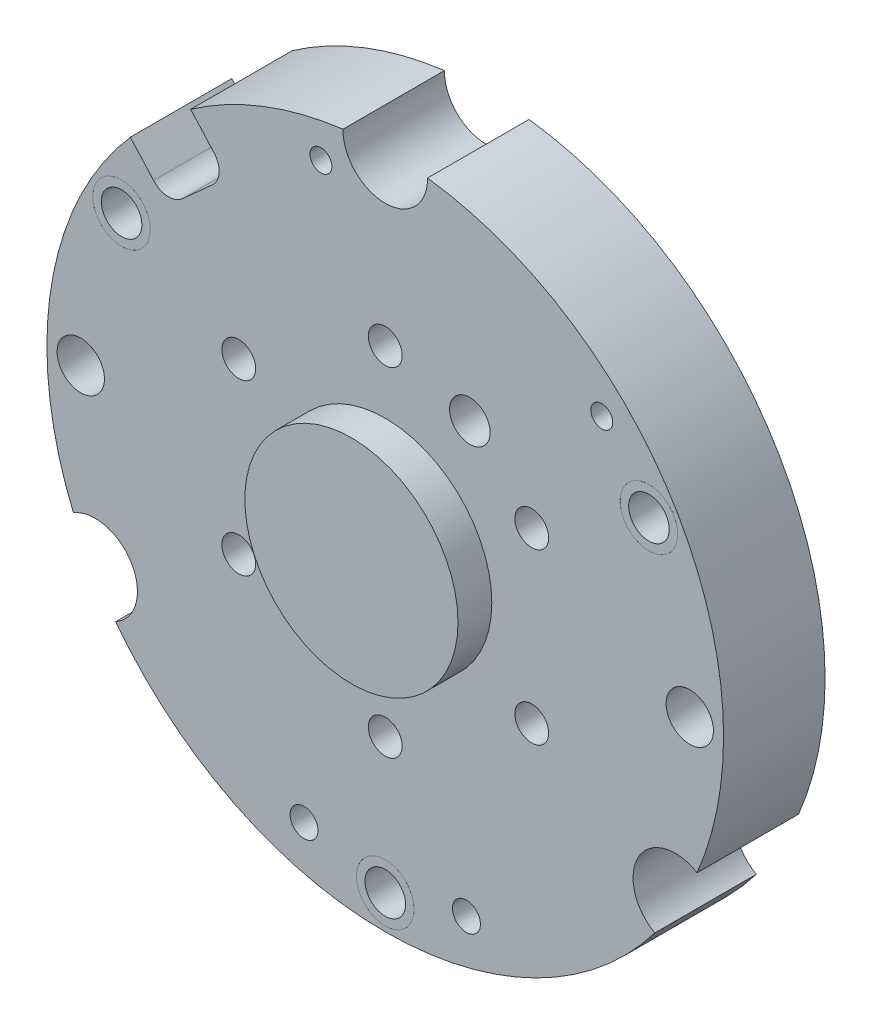
SolidWorks part; units mm, degrees
material "1060-H18"
ref_plane "Piano frontale" through (0, 0, 0) normal (0, 0, 1) x (1, 0, 0)
ref_plane "Piano superiore" through (0, 0, 0) normal (0, 1, 0) x (1, 0, 0)
ref_plane "Piano destro" through (0, 0, 0) normal (1, 0, 0) x (0, 0, -1)
sketch "Schizzo1" plane through (0, 0, 0) normal (0, 0, 1) x (1, 0, 0)
  line L3 (-34.2352, 29.0552) -> (-37.6736, 32.874)
  line L4 (-28.7559, 40.9035) -> (-25.3174, 37.0847)
  line L5 (-25.5395, 32.8479) -> (-29.9984, 28.8331)
  line L6 (-34.2352, 29.0552) -> (-37.6736, 32.874)
  line L7 (-28.7559, 40.9035) -> (-25.3174, 37.0847)
  line L8 (-25.5395, 32.8479) -> (-29.9984, 28.8331)
  arc A2 (32, 30.379) -> (32, 33.621) centre (32, 32) ccw
  arc A3 (32, 33.621) -> (32, 30.379) centre (32, 32) ccw
  arc A4 (32, 30.379) -> (32, 33.621) centre (32, 32) ccw
  arc A5 (32, 33.621) -> (32, 30.379) centre (32, 32) ccw
  arc A6 (-12, -44.067) -> (-12, -39.933) centre (-12, -42) ccw
  arc A7 (-12, -39.933) -> (-12, -44.067) centre (-12, -42) ccw
  arc A8 (-12, -44.067) -> (-12, -39.933) centre (-12, -42) ccw
  arc A9 (-34.2352, 29.0552) -> (-29.9984, 28.8331) centre (-32.0057, 31.0626) ccw
  arc A10 (-37.6736, 32.874) -> (-46.0866, -19.3913) centre (0, 0) ccw
  arc A11 (-39.8377, -30.2151) -> (-46.0866, -19.3913) centre (-42.87, -24.75) ccw
  arc A12 (-39.8377, -30.2151) -> (39.8377, -30.2151) centre (0, 0) ccw
  arc A13 (46.0866, -19.3913) -> (39.8377, -30.2151) centre (42.87, -24.75) ccw
  arc A14 (46.0866, -19.3913) -> (6.2491, 49.608) centre (0, 0) ccw
  arc A15 (-6.2491, 49.608) -> (6.2491, 49.608) centre (0, 49.5) ccw
  arc A16 (-6.2491, 49.608) -> (-28.7559, 40.9035) centre (0, 0) ccw
  arc A17 (-25.5395, 32.8479) -> (-25.3174, 37.0847) centre (-27.5469, 35.0773) ccw
  arc A18 (-34.2352, 29.0552) -> (-29.9984, 28.8331) centre (-32.0057, 31.0626) ccw
  arc A19 (-37.6736, 32.874) -> (-46.0866, -19.3913) centre (0, 0) ccw
  arc A20 (-39.8377, -30.2151) -> (-46.0866, -19.3913) centre (-42.87, -24.75) ccw
  arc A21 (-39.8377, -30.2151) -> (39.8377, -30.2151) centre (0, 0) ccw
  arc A22 (46.0866, -19.3913) -> (39.8377, -30.2151) centre (42.87, -24.75) ccw
  arc A23 (46.0866, -19.3913) -> (6.2491, 49.608) centre (0, 0) ccw
  arc A24 (-6.2491, 49.608) -> (6.2491, 49.608) centre (0, 49.5) ccw
  arc A25 (-6.2491, 49.608) -> (-28.7559, 40.9035) centre (0, 0) ccw
  arc A26 (-25.5395, 32.8479) -> (-25.3174, 37.0847) centre (-27.5469, 35.0773) ccw
  arc A27 (-12, -39.933) -> (-12, -44.067) centre (-12, -42) ccw
  arc A28 (12, -44.067) -> (12, -39.933) centre (12, -42) ccw
  arc A29 (12, -39.933) -> (12, -44.067) centre (12, -42) ccw
  arc A30 (12, -44.067) -> (12, -39.933) centre (12, -42) ccw
  arc A31 (12, -39.933) -> (12, -44.067) centre (12, -42) ccw
  arc A32 (-38.97, 26.75) -> (-38.97, 18.25) centre (-38.97, 22.5) ccw
  arc A33 (-38.97, 18.25) -> (-38.97, 26.75) centre (-38.97, 22.5) ccw
  arc A34 (-38.97, 26.75) -> (-38.97, 18.25) centre (-38.97, 22.5) ccw
  arc A35 (-38.97, 18.25) -> (-38.97, 26.75) centre (-38.97, 22.5) ccw
  arc A36 (38.97, 26.75) -> (38.97, 18.25) centre (38.97, 22.5) ccw
  arc A37 (38.97, 18.25) -> (38.97, 26.75) centre (38.97, 22.5) ccw
  arc A38 (38.97, 26.75) -> (38.97, 18.25) centre (38.97, 22.5) ccw
  arc A39 (38.97, 18.25) -> (38.97, 26.75) centre (38.97, 22.5) ccw
  arc A40 (0, -40.75) -> (0, -49.25) centre (0, -45) ccw
  arc A41 (0, -49.25) -> (0, -40.75) centre (0, -45) ccw
  arc A42 (0, -40.75) -> (0, -49.25) centre (0, -45) ccw
  arc A43 (0, -49.25) -> (0, -40.75) centre (0, -45) ccw
  arc A44 (-45, -3.5) -> (-45, 3.5) centre (-45, 0) ccw
  arc A45 (-45, 3.5) -> (-45, -3.5) centre (-45, 0) ccw
  arc A46 (-45, -3.5) -> (-45, 3.5) centre (-45, 0) ccw
  arc A47 (-45, 3.5) -> (-45, -3.5) centre (-45, 0) ccw
  arc A48 (45, -3.5) -> (45, 3.5) centre (45, 0) ccw
  arc A49 (45, 3.5) -> (45, -3.5) centre (45, 0) ccw
  arc A50 (45, -3.5) -> (45, 3.5) centre (45, 0) ccw
  arc A51 (45, 3.5) -> (45, -3.5) centre (45, 0) ccw
  arc A56 (-9.5, 42.379) -> (-9.5, 45.621) centre (-9.5, 44) ccw
  arc A57 (-9.5, 45.621) -> (-9.5, 42.379) centre (-9.5, 44) ccw
  arc A58 (-9.5, 42.379) -> (-9.5, 45.621) centre (-9.5, 44) ccw
  arc A59 (-9.5, 45.621) -> (-9.5, 42.379) centre (-9.5, 44) ccw
  dimension "D1" = 0
  dimension "D2" = 0
  dimension "D3" = 0
  dimension "D4" = 0
  dimension "D5" = 0
  dimension "D6" = 0
  dimension "D7" = 0
  dimension "D8" = 0
  dimension "D9" = 0
  dimension "D11" = 0
extrude "Estrusione-Estrusione1" add sketch "Schizzo1" along normal blind 15
sketch "Schizzo2" plane through (0, 0, 15) normal (0, 0, 1) x (1, 0, 0)
  arc A2 (-2.1651, -23.75) -> (2.1651, -26.25) centre (0, -25) ccw
  arc A3 (2.1651, -26.25) -> (-2.1651, -23.75) centre (0, -25) ccw
  arc A4 (-2.1651, -23.75) -> (2.1651, -26.25) centre (0, -25) ccw
  arc A5 (2.1651, -26.25) -> (-2.1651, -23.75) centre (0, -25) ccw
  arc A6 (19.4856, -11.25) -> (23.8157, -13.75) centre (21.6506, -12.5) ccw
  arc A7 (23.8157, -13.75) -> (19.4856, -11.25) centre (21.6506, -12.5) ccw
  arc A8 (19.4856, -11.25) -> (23.8157, -13.75) centre (21.6506, -12.5) ccw
  arc A9 (23.8157, -13.75) -> (19.4856, -11.25) centre (21.6506, -12.5) ccw
  arc A10 (19.4856, 13.75) -> (23.8157, 11.25) centre (21.6506, 12.5) ccw
  arc A11 (23.8157, 11.25) -> (19.4856, 13.75) centre (21.6506, 12.5) ccw
  arc A12 (19.4856, 13.75) -> (23.8157, 11.25) centre (21.6506, 12.5) ccw
  arc A13 (23.8157, 11.25) -> (19.4856, 13.75) centre (21.6506, 12.5) ccw
  arc A14 (9.9019, 23.1506) -> (15.0981, 20.1506) centre (12.5, 21.6506) ccw
  arc A15 (15.0981, 20.1506) -> (9.9019, 23.1506) centre (12.5, 21.6506) ccw
  arc A16 (9.9019, 23.1506) -> (15.0981, 20.1506) centre (12.5, 21.6506) ccw
  arc A17 (15.0981, 20.1506) -> (9.9019, 23.1506) centre (12.5, 21.6506) ccw
  arc A22 (-23.8157, -11.25) -> (-19.4856, -13.75) centre (-21.6506, -12.5) ccw
  arc A23 (-19.4856, -13.75) -> (-23.8157, -11.25) centre (-21.6506, -12.5) ccw
  arc A24 (-23.8157, -11.25) -> (-19.4856, -13.75) centre (-21.6506, -12.5) ccw
  arc A25 (-19.4856, -13.75) -> (-23.8157, -11.25) centre (-21.6506, -12.5) ccw
  arc A26 (-2.1651, 26.25) -> (2.1651, 23.75) centre (0, 25) ccw
  arc A27 (2.1651, 23.75) -> (-2.1651, 26.25) centre (0, 25) ccw
  arc A28 (-2.1651, 26.25) -> (2.1651, 23.75) centre (0, 25) ccw
  arc A29 (2.1651, 23.75) -> (-2.1651, 26.25) centre (0, 25) ccw
  arc A30 (-23.8157, 13.75) -> (-19.4856, 11.25) centre (-21.6506, 12.5) ccw
  arc A31 (-19.4856, 11.25) -> (-23.8157, 13.75) centre (-21.6506, 12.5) ccw
  arc A32 (-23.8157, 13.75) -> (-19.4856, 11.25) centre (-21.6506, 12.5) ccw
  arc A33 (-19.4856, 11.25) -> (-23.8157, 13.75) centre (-21.6506, 12.5) ccw
  dimension "D1" = 0
  dimension "D2" = 0
  dimension "D3" = 0
  dimension "D4" = 0
  dimension "D6" = 0
  dimension "D7" = 0
  dimension "D8" = 0
extrude "Taglio-Estrusione1" cut sketch "Schizzo2" against normal blind 15
sketch "Schizzo3" plane through (0, 0, 0) normal (0, 0, -1) x (-1, 0, 0)
  circle A74 centre (0, 25) radius 5.5
  circle A75 centre (0, 25) radius 5.5
  circle A85 centre (21.6506, 12.5) radius 5.5
  circle A86 centre (21.6506, -12.5) radius 5.5
  circle A87 centre (0, -25) radius 5.5
  circle A88 centre (-21.6506, -12.5) radius 5.5
  circle A89 centre (-21.6506, 12.5) radius 5.5
  dimension "D1" = 3
extrude "Taglio-Estrusione2" cut sketch "Schizzo3" against normal blind 5
sketch "Schizzo5" plane through (0, 0, 15) normal (0, 0, 1) x (1, 0, 0)
  arc A2 (13.6399, -7.875) -> (-13.6399, 7.875) centre (0, 0) ccw
  arc A3 (-13.6399, 7.875) -> (13.6399, -7.875) centre (0, 0) ccw
  arc A6 (13.6399, -7.875) -> (-13.6399, 7.875) centre (0, 0) ccw
  arc A7 (-13.6399, 7.875) -> (13.6399, -7.875) centre (0, 0) ccw
  dimension "D1" = 0
extrude "Estrusione-Estrusione2" add sketch "Schizzo5" along normal blind 5 separate body contours A7 A6
sketch "Schizzo6" plane through (0, 0, 0) normal (0, 0, -1) x (-1, 0, 0)
  circle A0 centre (0, 0) radius 35
extrude "Taglio-Estrusione3" cut sketch "Schizzo6" against normal blind 0.3
sketch "Schizzo7" plane through (0, 0, 0) normal (0, 0, -1) x (-1, 0, 0)
  circle A0 centre (38.97, 22.5) radius 3
  circle A1 centre (0.0006, -44.999) radius 3
  circle A2 centre (-38.9706, 22.499) radius 3
  circle A3 centre (38.97, 22.5) radius 4.25 construction
  circle A4 centre (0, -45) radius 4.25 construction
  circle A5 centre (-38.97, 22.5) radius 4.25 construction
  circle A6 centre (38.97, 22.5) radius 4.25
  circle A7 centre (0, -45) radius 4.25
  circle A8 centre (-38.97, 22.5) radius 4.25
  point P10 (0, 0)
  dimension "D1" = 6
  dimension "D2" = 3
extrude "Estrusione-Estrusione3" add sketch "Schizzo7" against normal blind 15 separate body
